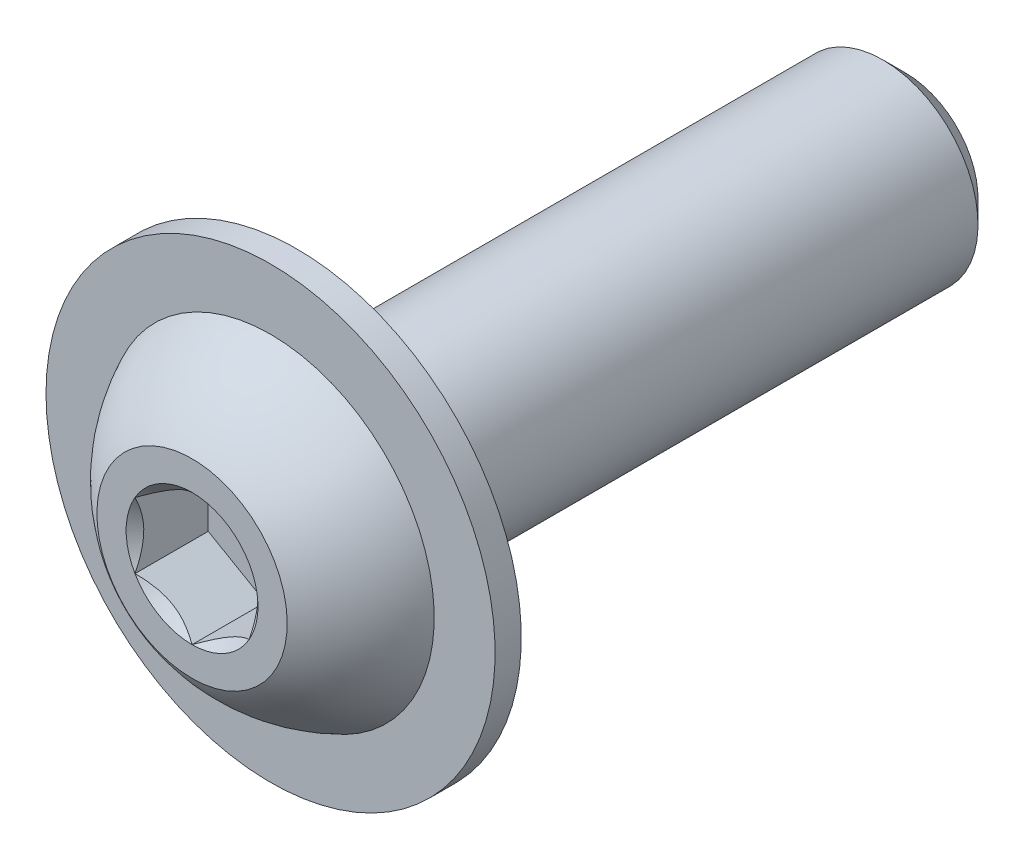
SolidWorks part; units mm, degrees
material "AISI 304"
ref_plane "Front" through (0, 0, 0) normal (0, 0, 1) x (1, 0, 0)
ref_plane "Top" through (0, 0, 0) normal (0, 1, 0) x (1, 0, 0)
ref_plane "Right" through (0, 0, 0) normal (1, 0, 0) x (0, 0, -1)
sketch "Sketch1" plane through (0, 0, 0) normal (1, 0, 0) x (0, 0, -1)
  line L2 (2.75, 2.5) -> (18.75, 2.5)
  line L3 (18.75, 2.5) -> (18.75, 0)
  line L4 (18.75, 0) -> (2.75, 0)
  line L6 (2.0625, 4.3) -> (2.75, 4.3) construction
  line L7 (18.75, 2.5) -> (18.75, -2.5) construction
  line L8 (0, 0) -> (2.75, 0) construction
  line L9 (2.75, 4.3) -> (2.75, -4.3) construction
  line L11 (2.75, 2.5) -> (2.75, 0)
  line L13 (0, 1.5) -> (0, -1.5) construction
  line L14 (0, 1.5) -> (0, 2.5) construction
  line L15 (2.0625, 4.3) -> (2.0625, 5.9) construction
  line L16 (2.0625, 5.9) -> (2.75, 5.9) construction
  line L17 (2.75, 5.9) -> (2.75, 4.3) construction
  line L18 (2.75, 5.9) -> (2.75, -5.9) construction
  arc A3 (0, 2.5) -> (2.0625, 4.3) centre (3.9985, 0) cw construction
  dimension "D1" = 0.6875
revolve "Revolve1" add sketch "Sketch1" angle 360 mid plane about L4
sketch "Sketch3" plane through (0, 0, -18.75) normal (0, 0, -1) x (-1, 0, 0)
  circle A0 centre (0, 0) radius 2.5
curve "Helix/Spiral1" pitch 0.8 height 16.8 turns 21
sketch "Sketch2" plane through (0, 0, 0) normal (1, 0, 0) x (0, 0, -1)
  line L0 (18.75, 2.5) -> (19.45, 2.5)
  line L1 (19.45, 2.5) -> (19.15, 1.9804)
  line L2 (19.15, 1.9804) -> (19.05, 1.9804)
  line L3 (19.05, 1.9804) -> (18.75, 2.5)
  line L4 (18.9, 2.2402) -> (19.3, 2.2402) construction
  dimension "D1" = 60
  dimension "D2" = 0.1
  dimension "D3" = 0.4
chamfer "Chamfer1" distance 0.6 angle 45 1 edges at (0, 2.5, -18.75)
sweep "Cut-Sweep1" [suppressed] cut profiles "Sketch2" path "Helix/Spiral1"
sketch "Sketch7" plane through (0, 0, 0) normal (1, 0, 0) x (0, 0, -1)
  line L6 (2.0625, 4.3) -> (2.75, 4.3) construction
  line L8 (0, 0) -> (2.75, 0) construction
  line L11 (2.75, 4.3) -> (2.75, -4.3) construction
  line L12 (2.0625, 4.3) -> (2.75, 4.3)
  line L13 (0, 0) -> (2.75, 0)
  line L14 (0, 1.5) -> (0, -1.5) construction
  line L15 (2.75, 4.3) -> (2.75, 0)
  line L16 (0, 2.5) -> (0, 0)
  arc A2 (2.0625, 4.3) -> (0, 2.5) centre (3.9985, 0) ccw construction
  arc A3 (2.0625, 4.3) -> (0, 2.5) centre (3.9985, 0) ccw
revolve "Revolve2" add sketch "Sketch7" angle 360 mid plane about L13
sketch "Sketch11" plane through (0, 0, -2.75) normal (0, 0, -1) x (-1, 0, 0)
  circle A0 centre (0, 0) radius 5.9
extrude "Boss-Extrude3" add sketch "Sketch11" against normal up to vertex (0.6875 mm away) up to point (0, 4.3, -2.0625)
sketch "Sketch5" plane through (0, 0, 0) normal (0, 0, 1) x (1, 0, 0)
  line L1 (1.5, -0.866) -> (1.5, 0.866)
  line L2 (1.5, 0.866) -> (0, 1.7321)
  line L3 (0, 1.7321) -> (-1.5, 0.866)
  line L4 (-1.5, 0.866) -> (-1.5, -0.866)
  line L5 (-1.5, -0.866) -> (0, -1.7321)
  line L6 (0, -1.7321) -> (1.5, -0.866)
  circle A0 centre (0, 0) radius 1.5 construction
extrude "Cut-Extrude2" cut sketch "Sketch5" against normal blind 1.925
sketch "Sketch6" plane through (0, 0, 0) normal (0, 0, 1) x (1, 0, 0)
  circle A0 centre (0, 0) radius 1.7321
extrude "Cut-Extrude3" cut sketch "Sketch6" against normal blind 1.925 draft 45
sketch "Sketch9" [suppressed] plane through (0, 0, -5.0546) normal (0, 0, 1) x (1, 0, 0)
  circle A2 centre (0, 0) radius 4.7625
extrude "Boss-Extrude2" [suppressed] add sketch "Sketch9" against normal offset from surface (6.35 mm away) 31.75
sketch "Sketch10" plane through (0, 0, 0) normal (1, 0, 0) x (0, 0, -1)
  line L0 (18.75, 2.5) -> (18.75, -2.5) construction
  point P0 (17.55, -2.5)
  dimension "D1" = 1.2
equation "\"D3@Helix/Spiral1\" = \"Lg@Sketch1\" + \"D4@Helix/Spiral1\""
equation "\"D2@Sketch2\" = \"D4@Helix/Spiral1\" * .125"
equation "\"D3@Sketch2\" = \"D4@Helix/Spiral1\" * .5"
equation "\"D1@Chamfer1\" = \"D4@Helix/Spiral1\" * .75"
equation "\"D1@Cut-Extrude2\" = \"Head Ht@Sketch1\" * .7"
equation "\"D1@Sketch1\" = \"Head Ht@Sketch1\" * .25"
equation "\"D1@Sketch10\" = \"D4@Helix/Spiral1\" * 1.5"
equation "\"D1@Cut-Extrude3\" = \"D1@Cut-Extrude2\""
